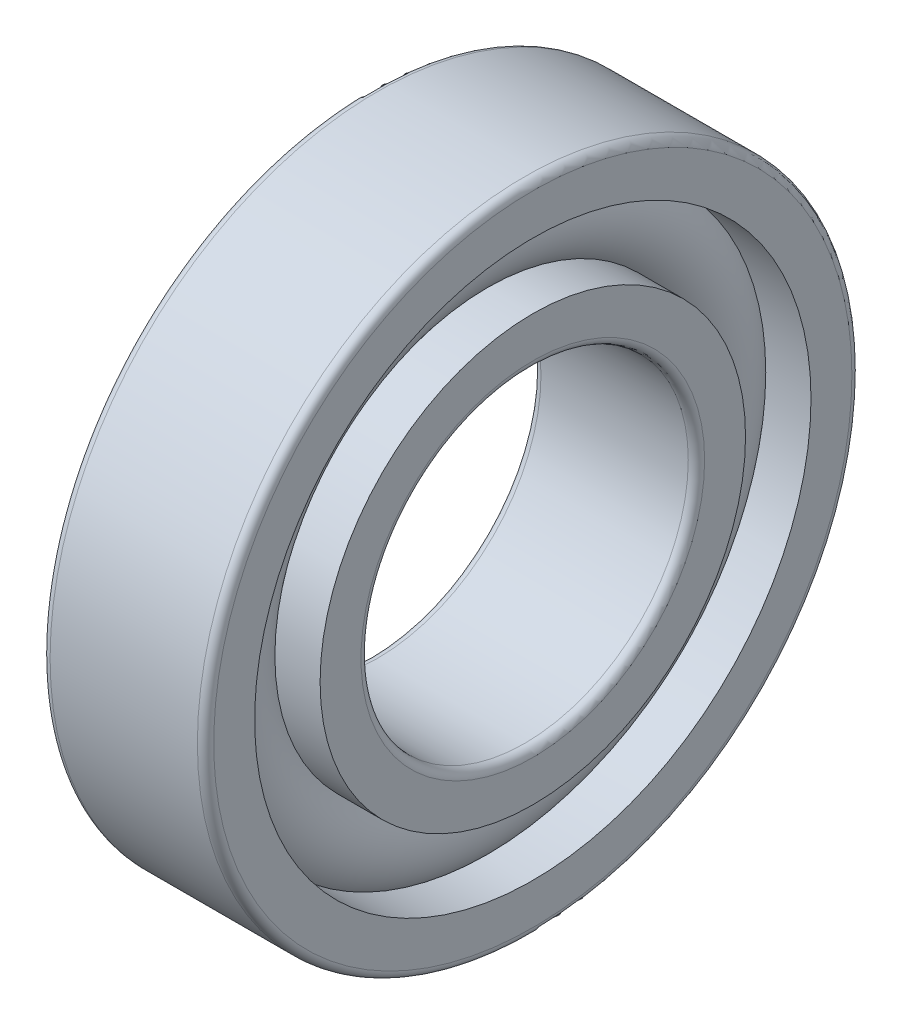
SolidWorks part; units mm, degrees
ref_plane "Plane1" through (0, 0, 0) normal (0, 0, 1) x (1, 0, 0)
ref_plane "Plane2" through (0, 0, 0) normal (0, 1, 0) x (1, 0, 0)
ref_plane "Plane3" through (0, 0, 0) normal (1, 0, 0) x (0, 0, -1)
sketch "Clipboard" plane through (0, 0, 0) normal (0, 0, 1) x (1, 0, 0)
  line L0 (-10, 0) -> (10, 0) construction
  line L1 (0, 0) -> (22.3471, -0.7804)
  line L2 (0, 0) -> (5.9963, 0.2094)
  line L3 (0, 0) -> (22.3471, -0.7804)
  line L4 (0, 0) -> (-22.3573, -0.3902)
  dimension "BallCLRad" = 6
  dimension "Count" = 2
  dimension "Show_count" = 2
  dimension "Max_count" = 2
  dimension "Min_count" = 1
sketch "CagSpiSke" plane through (0, 0, 0) normal (0, 0, 1) x (1, 0, 0)
  line L0 (0.12, 5.8) -> (0.12, 6.2)
  line L1 (0.12, 6.2) -> (-0.12, 6.2)
  line L2 (-0.12, 6.2) -> (-0.12, 5.8)
  line L3 (-0.12, 5.8) -> (0.12, 5.8)
  line L4 (-20.6375, 0) -> (20.6375, 0) construction
  line L5 (0, 0) -> (0, 23.7692) construction
  dimension "Thickness" = 0.24
  dimension "OD" = 12.4
  dimension "ID" = 11.6
revolve "CageSpine" add sketch "CagSpiSke" angle 0.001 about L4 reverse direction yes
ref_axis "Axis1" through (-50, 0, 0) along (1, 0, 0)
sketch "CagBalSke" plane through (0, 0, 0) normal (0, 0, 1) x (1, 0, 0)
  line L0 (-1.32, 6) -> (1.32, 6)
  line L1 (-1.905, 6) -> (1.905, 6) construction
  line L2 (-10, 0) -> (10, 0) construction
  line L3 (0, 0) -> (0, 24) construction
  arc A0 (1.32, 6) -> (-1.32, 6) centre (0, 6) cw
  dimension "CageWallOD" = 2.64
  dimension "BallCLRad" = 6
revolve "CageBall" [suppressed] add sketch "CagBalSke" angle 360 about L1 reverse direction yes
pattern_circular "CageBalls" [suppressed] count 2 every 180 about axis through (-50, 0, 0) along (1, 0, 0)
sketch "CagTrmODSke" plane through (0, 0, 0) normal (0, 0, 1) x (1, 0, 0)
  line L0 (1.321, 6.2) -> (1.321, 7.321)
  line L1 (1.321, 7.321) -> (-1.321, 7.321)
  line L2 (-1.321, 7.321) -> (-1.321, 6.2)
  line L3 (-1.321, 6.2) -> (1.321, 6.2)
  line L4 (-20.6375, 0) -> (20.6375, 0) construction
  line L5 (0, 0) -> (0, 25) construction
  dimension "Width" = 2.642
  dimension "ID" = 12.4
  dimension "OD" = 14.642
revolve "CageTrimOD" [suppressed] cut sketch "CagTrmODSke" angle 360 about L4 reverse direction yes
sketch "CagTrmIDSke" plane through (0, 0, 0) normal (0, 0, 1) x (1, 0, 0)
  line L0 (1.321, 4.681) -> (1.321, 5.8)
  line L1 (1.321, 5.8) -> (-1.321, 5.8)
  line L2 (-1.321, 5.8) -> (-1.321, 4.681)
  line L3 (-1.321, 4.681) -> (1.321, 4.681)
  line L4 (-20.6375, 0) -> (20.6375, 0) construction
  line L5 (0, 0) -> (0, 25) construction
  dimension "ID" = 9.362
  dimension "OD" = 11.6
  dimension "Width" = 2.642
revolve "CageTrimID" [suppressed] cut sketch "CagTrmIDSke" angle 360 about L4 reverse direction yes
sketch "BalSimSke" plane through (0, 0, 0) normal (0, 0, 1) x (1, 0, 0)
  line L0 (-10, 0) -> (10, 0) construction
  line L1 (-10, 6) -> (10, 6) construction
  line L2 (0, 0) -> (0, 23) construction
  circle A0 centre (0, 6) radius 1.2
  dimension "Ball_diameter" = 2.4
  dimension "BallCLRad" = 6
revolve "BallsSimplified" add sketch "BalSimSke" angle 360 about L0
sketch "BalDetSke" plane through (0, 0, 0) normal (0, 0, 1) x (1, 0, 0)
  line L0 (-1.2, 6) -> (1.2, 6)
  line L1 (-1.905, 6) -> (1.905, 6) construction
  line L2 (0, 0) -> (0, 25) construction
  arc A0 (1.2, 6) -> (-1.2, 6) centre (0, 6) cw
  dimension "Ball_diameter" = 2.4
  dimension "BallCLRad" = 6
revolve "BallDetailed" [suppressed] add sketch "BalDetSke" angle 360 about L1 reverse direction yes
sketch "InnRacSke" plane through (0, 0, 0) normal (0, 0, 1) x (1, 0, 0)
  line L0 (-0.8606, 5.2) -> (-2, 5.2)
  line L1 (-2, 5.2) -> (-2, 4.2)
  line L2 (-1.8, 4) -> (1.8, 4)
  line L3 (2, 4.2) -> (2, 5.2)
  line L4 (2, 5.2) -> (0.8606, 5.2)
  line L5 (-20.6375, 0) -> (20.6375, 0) construction
  line L6 (0, 0) -> (0, 30) construction
  arc A0 (-2, 4.2) -> (-1.8, 4) centre (-1.8, 4.2) ccw
  arc A1 (1.8, 4) -> (2, 4.2) centre (1.8, 4.2) ccw
  arc A2 (0.8606, 5.2) -> (-0.8606, 5.2) centre (0, 6) cw
  dimension "Fillet_radius" = 0.2
  dimension "Ball_diameter" = 2.35
  dimension "ID" = 8
  dimension "OD" = 10.4
  dimension "Width" = 4
  dimension "BallCLRad" = 6
revolve "InnerRace" add sketch "InnRacSke" angle 360 about L5 reverse direction yes
sketch "OutRacSke" plane through (0, 0, 0) normal (0, 0, 1) x (1, 0, 0)
  line L0 (-0.8606, 6.8) -> (-2, 6.8)
  line L1 (-2, 6.8) -> (-2, 7.8)
  line L2 (-1.8, 8) -> (1.8, 8)
  line L3 (2, 7.8) -> (2, 6.8)
  line L4 (2, 6.8) -> (0.8606, 6.8)
  line L5 (-20.6375, 0) -> (20.6375, 0) construction
  line L6 (0, 0) -> (0, 30) construction
  arc A0 (-2, 7.8) -> (-1.8, 8) centre (-1.8, 7.8) cw
  arc A1 (1.8, 8) -> (2, 7.8) centre (1.8, 7.8) cw
  arc A2 (0.8606, 6.8) -> (-0.8606, 6.8) centre (0, 6) ccw
  dimension "Fillet_radius" = 0.2
  dimension "Ball_diameter" = 2.35
  dimension "OD" = 16
  dimension "ID" = 13.6
  dimension "Width" = 4
  dimension "BallCLRad" = 6
revolve "OuterRace" add sketch "OutRacSke" angle 360 about L5 reverse direction yes
pattern_circular "BallsDetailed" [suppressed] count 2 every 180 about axis through (-50, 0, 0) along (1, 0, 0)
equation "\"BallCLRad@Clipboard\" = ( \"OD@OutRacSke\" + \"ID@InnRacSke\" ) / 4"
equation "\"BallCLRad@BalSimSke\" = \"BallCLRad@Clipboard\""
equation "\"BallCLRad@BalDetSke\" = \"BallCLRad@Clipboard\""
equation "\"BallCLRad@InnRacSke\" = \"BallCLRad@Clipboard\""
equation "\"BallCLRad@OutRacSke\" = \"BallCLRad@Clipboard\""
equation "\"Ball_diameter@InnRacSke\" = \"Ball_diameter@BalDetSke\" - 0.05"
equation "\"Ball_diameter@OutRacSke\" = \"Ball_diameter@BalDetSke\" - 0.05"
equation "\"Ball_diameter@BalSimSke\" = \"Ball_diameter@BalDetSke\""
equation "\"Width@OutRacSke\" = \"Width@InnRacSke\""
equation "\"Fillet_radius@OutRacSke\" = \"Fillet_radius@InnRacSke\""
equation "\"Max_count@Clipboard\" = int( 3.14159265 / atn(( \"Ball_diameter@BalDetSke\" / 2) / sqr( \"BallCLRad@Clipboard\"  *  \"BallCLRad@Clipboard\" - ( \"Ball_diameter@BalDetSke\" / 2) *  ( \"Ball_diameter@BalDetSke\" / 2))))"
equation "\"Max_count@Clipboard\" = ((sgn( \"Max_count@Clipboard\" - \"Count@Clipboard\" )-1)*( \"Max_count@Clipboard\" - \"Count@Clipboard\" ))/-2+ \"Count@Clipboard\""
equation "\"Count@BallsDetailed\" = int( \"Show_count@Clipboard\" ) "
equation "\"Count@BallsDetailed\" = ((sgn( \"Count@BallsDetailed\" - \"Max_count@Clipboard\" )-1)*( \"Count@BallsDetailed\" - \"Max_count@Clipboard\" ))/-2+ \"Max_count@Clipboard\""
equation "\"Count@BallsDetailed\" = ((sgn( \"Count@BallsDetailed\" - \"Min_count@Clipboard\" )+1)*( \"Count@BallsDetailed\" - \"Min_count@Clipboard\"))/2 +\"Min_count@Clipboard\""
equation "\"Angle@BallsDetailed\" = 360.0 / \"Max_count@Clipboard\""
equation "\"BallCLRad@CagBalSke\" = \"BallCLRad@Clipboard\""
equation "\"Count@CageBalls\" = \"Count@BallsDetailed\""
equation "\"Angle@CageBalls\" = \"Angle@BallsDetailed\""
equation "\"Angle@CageSpine\" =  \"Angle@CageBalls\" * ( \"Count@CageBalls\" -1 + int( \"Count@CageBalls\" / \"Max_count@Clipboard\" ) )  + 0.001 -  int( \"Count@CageBalls\" / \"Max_count@Clipboard\" ) * 0.001"
equation "\"Angle@CageSpine\" =  \"Angle@CageSpine\" * int( \"Min_count@Clipboard\" / 2) + int(1 / \"Min_count@Clipboard\")  * 0.001"
equation "\"CageWallOD@CagBalSke\" =  \"Ball_diameter@BalDetSke\" * 1.1"
equation "\"Thickness@CagSpiSke\" =  \"Ball_diameter@BalDetSke\" * 0.1"
equation "\"OD@CagTrmODSke\" = \"BallCLRad@Clipboard\" * 2 + \"CageWallOD@CagBalSke\" + 0.002"
equation "\"ID@CagTrmODSke\" = \"BallCLRad@Clipboard\" * 2 + \"Ball_diameter@BalDetSke\" / 6"
equation "\"OD@CagTrmIDSke\" = \"BallCLRad@Clipboard\" * 2 - \"Ball_diameter@BalDetSke\" / 6"
equation "\"ID@CagTrmIDSke\" = \"BallCLRad@Clipboard\" * 2 - \"CageWallOD@CagBalSke\" + 0.002"
equation "\"OD@CagSpiSke\" = \"ID@CagTrmODSke\""
equation "\"ID@CagSpiSke\" = \"OD@CagTrmIDSke\""
equation "\"Width@CagTrmODSke\" = \"CageWallOD@CagBalSke\" + 0.002"
equation "\"Width@CagTrmIDSke\" = \"CageWallOD@CagBalSke\" + 0.002"
